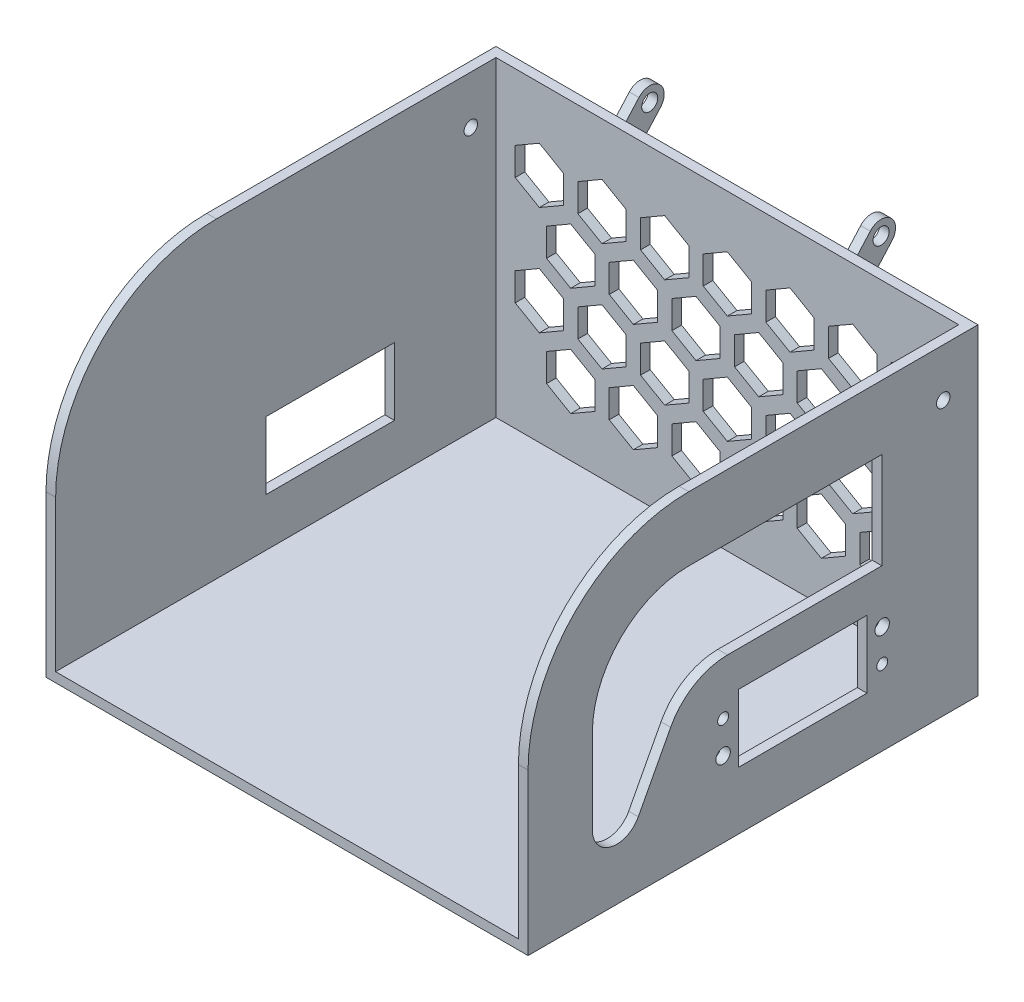
SolidWorks part; units mm, degrees
material "PLA"
ref_plane "Front Plane" through (0, 0, 0) normal (0, 0, 1) x (1, 0, 0)
ref_plane "Top Plane" through (0, 0, 0) normal (0, 1, 0) x (1, 0, 0)
ref_plane "Right Plane" through (0, 0, 0) normal (1, 0, 0) x (0, 0, -1)
sketch "Sketch1" plane through (0, 0, 0) normal (1, 0, 0) x (0, 0, -1)
  line L0 (0, 0) -> (-140, 0)
  line L1 (-140, 0) -> (-140, 50)
  line L2 (-90, 100) -> (0, 100)
  line L3 (0, 100) -> (0, 0)
  arc A0 (-140, 50) -> (-90, 100) centre (-90, 50) cw
  dimension "D1" = 140
  dimension "D2" = 100
  dimension "D3" = 50
extrude "Boss-Extrude1" add sketch "Sketch1" along normal blind 150 contours A0 L2 L3 L0 L1
sketch "Sketch2" plane through (0, 100, 0) normal (0, 1, 0) x (1, 0, 0)
  line L0 (150, 0) -> (0, 0) construction
  line L1 (3, -3) -> (147, -3)
  line L2 (3, -3) -> (3, -145)
  line L3 (3, -145) -> (147, -145)
  line L4 (147, -3) -> (147, -145)
  line L5 (150, -90) -> (150, 0) construction
  line L6 (0, -90) -> (0, 0) construction
  line L8 (150, -140) -> (0, -140) construction
  dimension "D1" = 3
  dimension "D2" = 3
  dimension "D3" = 3
  dimension "D4" = 5
extrude "Cut-Extrude1" cut sketch "Sketch2" against normal offset from surface (97 mm away) 3 up to face at (75, 0, 70)
ref_plane "Plane1" through (75, 0, 0) normal (1, 0, 0) x (0, 0, -1)
ref_plane "Plane2" through (111, 0, 0) normal (1, 0, 0) x (0, 0, -1)
ref_plane "Plane3" through (39, 0, 0) normal (1, 0, 0) x (0, 0, -1)
sketch "Sketch3" plane through (111, 0, 0) normal (1, 0, 0) x (0, 0, -1)
  line L0 (0, 100) -> (0, 86.4837)
  line L1 (0, 86.4837) -> (10.7098, 98.4837)
  line L2 (3.9952, 104.4764) -> (0, 100)
  arc A0 (10.7098, 98.4837) -> (3.9952, 104.4764) centre (7.3525, 101.4801) ccw
  circle A1 centre (7.3525, 101.4801) radius 2.5
  dimension "D1" = 2
  dimension "D2" = 5
  dimension "D3" = 6
  dimension "D4" = 12
extrude "Boss-Extrude2" add sketch "Sketch3" along normal mid plane 3
mirror "Mirror1" about plane through (75, 0, 0) normal (1, 0, 0) of "Boss-Extrude2"
sketch "Sketch4" plane through (150, 0, 0) normal (1, 0, 0) x (0, 0, -1)
  line L0 (-10.8107, 85.0634) -> (-67.3793, 28.4949) construction
  line L1 (-74.5612, 38.9949) -> (-74.5612, 17.9949)
  line L2 (-74.5612, 17.9949) -> (-34.5612, 17.9949)
  line L3 (0, 0) -> (-140, 0) construction
  line L4 (-34.5612, 17.9949) -> (-34.5612, 38.9949)
  line L5 (-34.5612, 38.9949) -> (-74.5612, 38.9949)
  circle A0 centre (-67.3793, 28.4949) radius 2.5
  circle A1 centre (-10.8107, 85.0634) radius 2.1
  point P8 (-74.5612, 28.4949)
  dimension "D4" = 4.2
  dimension "D5" = 5
  dimension "D1" = 80
  dimension "D2" = 45
  dimension "D3" = 40
  dimension "D6" = 21
extrude "Cut-Extrude2" cut sketch "Sketch4" against normal up to next contours A0 | A1 | L4 L5 A0 L1 L2 region at (150, 28.4949, 54.2544) region at (150, 28.4949, 67.3793) region at (150, 85.0634, 10.8107)
mirror "Mirror2" about plane through (75, 0, 0) normal (1, 0, 0) of "Cut-Extrude2"
sketch "Sketch5" plane through (0, 0, 0) normal (0, 0, -1) x (-1, 0, 0)
  line L0 (-150, 75) -> (0, 75) construction
  line L1 (-150, 100) -> (-150, 0) construction
  line L2 (0, 100) -> (0, 0) construction
  line L3 (-75, 100) -> (-75, 0) construction
  line L4 (-109.5, 100) -> (-40.5, 100) construction
  line L5 (-75, 91.3518) -> (-75, -91.3518) construction
  line L6 (-114, 83.6603) -> (-121.5, 79.3301)
  line L7 (-133.5, 83.6603) -> (-141, 79.3301)
  line L8 (-141, 79.3301) -> (-141, 70.6699)
  line L9 (-141, 70.6699) -> (-133.5, 66.3397)
  line L10 (-133.5, 66.3397) -> (-126, 70.6699)
  line L11 (-126, 70.6699) -> (-126, 79.3301)
  line L12 (-126, 79.3301) -> (-133.5, 83.6603)
  line L13 (-121.5, 79.3301) -> (-121.5, 70.6699)
  line L14 (-121.5, 70.6699) -> (-114, 66.3397)
  line L15 (-114, 66.3397) -> (-106.5, 70.6699)
  line L16 (-106.5, 70.6699) -> (-106.5, 79.3301)
  line L17 (-106.5, 79.3301) -> (-114, 83.6603)
  line L18 (-94.5, 83.6603) -> (-102, 79.3301)
  line L19 (-102, 79.3301) -> (-102, 70.6699)
  line L20 (-102, 70.6699) -> (-94.5, 66.3397)
  line L21 (-94.5, 66.3397) -> (-87, 70.6699)
  line L22 (-87, 70.6699) -> (-87, 79.3301)
  line L23 (-87, 79.3301) -> (-94.5, 83.6603)
  line L24 (-75, 83.6603) -> (-82.5, 79.3301)
  line L25 (-82.5, 79.3301) -> (-82.5, 70.6699)
  line L26 (-82.5, 70.6699) -> (-75, 66.3397)
  line L27 (-75, 66.3397) -> (-67.5, 70.6699)
  line L28 (-67.5, 70.6699) -> (-67.5, 79.3301)
  line L29 (-67.5, 79.3301) -> (-75, 83.6603)
  line L30 (-55.5, 83.6603) -> (-63, 79.3301)
  line L31 (-63, 79.3301) -> (-63, 70.6699)
  line L32 (-63, 70.6699) -> (-55.5, 66.3397)
  line L33 (-55.5, 66.3397) -> (-48, 70.6699)
  line L34 (-48, 70.6699) -> (-48, 79.3301)
  line L35 (-48, 79.3301) -> (-55.5, 83.6603)
  line L36 (-36, 83.6603) -> (-43.5, 79.3301)
  line L37 (-43.5, 79.3301) -> (-43.5, 70.6699)
  line L38 (-43.5, 70.6699) -> (-36, 66.3397)
  line L39 (-36, 66.3397) -> (-28.5, 70.6699)
  line L40 (-28.5, 70.6699) -> (-28.5, 79.3301)
  line L41 (-28.5, 79.3301) -> (-36, 83.6603)
  line L42 (-16.5, 83.6603) -> (-24, 79.3301)
  line L43 (-24, 79.3301) -> (-24, 70.6699)
  line L44 (-24, 70.6699) -> (-16.5, 66.3397)
  line L45 (-16.5, 66.3397) -> (-9, 70.6699)
  line L46 (-9, 70.6699) -> (-9, 79.3301)
  line L47 (-9, 79.3301) -> (-16.5, 83.6603)
  line L48 (-150, 58.1125) -> (0, 58.1125) construction
  line L49 (-123.75, 58.1125) -> (-123.75, 75) construction
  line L50 (-123.75, 66.7728) -> (-131.25, 62.4426)
  line L51 (-131.25, 62.4426) -> (-131.25, 53.7824)
  line L52 (-131.25, 53.7824) -> (-123.75, 49.4523)
  line L53 (-123.75, 49.4523) -> (-116.25, 53.7824)
  line L54 (-116.25, 53.7824) -> (-116.25, 62.4426)
  line L55 (-116.25, 62.4426) -> (-123.75, 66.7728)
  line L56 (-37.5, 100) -> (0, 100) construction
  line L57 (-104.25, 66.7728) -> (-111.75, 62.4426)
  line L58 (-111.75, 62.4426) -> (-111.75, 53.7824)
  line L59 (-111.75, 53.7824) -> (-104.25, 49.4523)
  line L60 (-104.25, 49.4523) -> (-96.75, 53.7824)
  line L61 (-96.75, 53.7824) -> (-96.75, 62.4426)
  line L62 (-96.75, 62.4426) -> (-104.25, 66.7728)
  line L63 (-84.75, 66.7728) -> (-92.25, 62.4426)
  line L64 (-92.25, 62.4426) -> (-92.25, 53.7824)
  line L65 (-92.25, 53.7824) -> (-84.75, 49.4523)
  line L66 (-84.75, 49.4523) -> (-77.25, 53.7824)
  line L67 (-77.25, 53.7824) -> (-77.25, 62.4426)
  line L68 (-77.25, 62.4426) -> (-84.75, 66.7728)
  line L69 (-65.25, 66.7728) -> (-72.75, 62.4426)
  line L70 (-72.75, 62.4426) -> (-72.75, 53.7824)
  line L71 (-72.75, 53.7824) -> (-65.25, 49.4523)
  line L72 (-65.25, 49.4523) -> (-57.75, 53.7824)
  line L73 (-57.75, 53.7824) -> (-57.75, 62.4426)
  line L74 (-57.75, 62.4426) -> (-65.25, 66.7728)
  line L75 (-45.75, 66.7728) -> (-53.25, 62.4426)
  line L76 (-53.25, 62.4426) -> (-53.25, 53.7824)
  line L77 (-53.25, 53.7824) -> (-45.75, 49.4523)
  line L78 (-45.75, 49.4523) -> (-38.25, 53.7824)
  line L79 (-38.25, 53.7824) -> (-38.25, 62.4426)
  line L80 (-38.25, 62.4426) -> (-45.75, 66.7728)
  line L81 (-26.25, 66.7728) -> (-33.75, 62.4426)
  line L82 (-33.75, 62.4426) -> (-33.75, 53.7824)
  line L83 (-33.75, 53.7824) -> (-26.25, 49.4523)
  line L84 (-26.25, 49.4523) -> (-18.75, 53.7824)
  line L85 (-18.75, 53.7824) -> (-18.75, 62.4426)
  line L86 (-18.75, 62.4426) -> (-26.25, 66.7728)
  line L87 (-9, 36.8949) -> (-16.5, 32.5648)
  line L88 (-9, 45.5551) -> (-9, 36.8949)
  line L89 (-16.5, 49.8853) -> (-9, 45.5551)
  line L90 (-24, 45.5551) -> (-16.5, 49.8853)
  line L91 (-24, 36.8949) -> (-24, 45.5551)
  line L92 (-16.5, 32.5648) -> (-24, 36.8949)
  line L93 (-28.5, 36.8949) -> (-36, 32.5648)
  line L94 (-28.5, 45.5551) -> (-28.5, 36.8949)
  line L95 (-36, 49.8853) -> (-28.5, 45.5551)
  line L96 (-43.5, 45.5551) -> (-36, 49.8853)
  line L97 (-43.5, 36.8949) -> (-43.5, 45.5551)
  line L98 (-36, 32.5648) -> (-43.5, 36.8949)
  line L99 (-48, 36.8949) -> (-55.5, 32.5648)
  line L100 (-48, 45.5551) -> (-48, 36.8949)
  line L101 (-55.5, 49.8853) -> (-48, 45.5551)
  line L102 (-63, 45.5551) -> (-55.5, 49.8853)
  line L103 (-63, 36.8949) -> (-63, 45.5551)
  line L104 (-55.5, 32.5648) -> (-63, 36.8949)
  line L105 (-67.5, 36.8949) -> (-75, 32.5648)
  line L106 (-67.5, 45.5551) -> (-67.5, 36.8949)
  line L107 (-75, 49.8853) -> (-67.5, 45.5551)
  line L108 (-82.5, 45.5551) -> (-75, 49.8853)
  line L109 (-82.5, 36.8949) -> (-82.5, 45.5551)
  line L110 (-75, 32.5648) -> (-82.5, 36.8949)
  line L111 (-87, 36.8949) -> (-94.5, 32.5648)
  line L112 (-87, 45.5551) -> (-87, 36.8949)
  line L113 (-94.5, 49.8853) -> (-87, 45.5551)
  line L114 (-102, 45.5551) -> (-94.5, 49.8853)
  line L115 (-102, 36.8949) -> (-102, 45.5551)
  line L116 (-94.5, 32.5648) -> (-102, 36.8949)
  line L117 (-106.5, 36.8949) -> (-114, 32.5648)
  line L118 (-106.5, 45.5551) -> (-106.5, 36.8949)
  line L119 (-114, 49.8853) -> (-106.5, 45.5551)
  line L120 (-121.5, 45.5551) -> (-114, 49.8853)
  line L121 (-121.5, 36.8949) -> (-121.5, 45.5551)
  line L122 (-114, 32.5648) -> (-121.5, 36.8949)
  line L123 (-126, 36.8949) -> (-133.5, 32.5648)
  line L124 (-126, 45.5551) -> (-126, 36.8949)
  line L125 (-133.5, 49.8853) -> (-126, 45.5551)
  line L126 (-141, 45.5551) -> (-133.5, 49.8853)
  line L127 (-141, 36.8949) -> (-141, 45.5551)
  line L128 (-133.5, 32.5648) -> (-141, 36.8949)
  line L129 (-141, 41.225) -> (-9, 41.225) construction
  line L130 (-18.75, 20.0074) -> (-26.25, 15.6773)
  line L131 (-18.75, 28.6676) -> (-18.75, 20.0074)
  line L132 (-26.25, 32.9978) -> (-18.75, 28.6676)
  line L133 (-33.75, 28.6676) -> (-26.25, 32.9978)
  line L134 (-33.75, 20.0074) -> (-33.75, 28.6676)
  line L135 (-26.25, 15.6773) -> (-33.75, 20.0074)
  line L136 (-38.25, 20.0074) -> (-45.75, 15.6773)
  line L137 (-38.25, 28.6676) -> (-38.25, 20.0074)
  line L138 (-45.75, 32.9978) -> (-38.25, 28.6676)
  line L139 (-53.25, 28.6676) -> (-45.75, 32.9978)
  line L140 (-53.25, 20.0074) -> (-53.25, 28.6676)
  line L141 (-45.75, 15.6773) -> (-53.25, 20.0074)
  line L142 (-57.75, 20.0074) -> (-65.25, 15.6773)
  line L143 (-57.75, 28.6676) -> (-57.75, 20.0074)
  line L144 (-65.25, 32.9978) -> (-57.75, 28.6676)
  line L145 (-72.75, 28.6676) -> (-65.25, 32.9978)
  line L146 (-72.75, 20.0074) -> (-72.75, 28.6676)
  line L147 (-65.25, 15.6773) -> (-72.75, 20.0074)
  line L148 (-77.25, 20.0074) -> (-84.75, 15.6773)
  line L149 (-77.25, 28.6676) -> (-77.25, 20.0074)
  line L150 (-84.75, 32.9978) -> (-77.25, 28.6676)
  line L151 (-92.25, 28.6676) -> (-84.75, 32.9978)
  line L152 (-92.25, 20.0074) -> (-92.25, 28.6676)
  line L153 (-84.75, 15.6773) -> (-92.25, 20.0074)
  line L154 (-96.75, 20.0074) -> (-104.25, 15.6773)
  line L155 (-96.75, 28.6676) -> (-96.75, 20.0074)
  line L156 (-104.25, 32.9978) -> (-96.75, 28.6676)
  line L157 (-111.75, 28.6676) -> (-104.25, 32.9978)
  line L158 (-111.75, 20.0074) -> (-111.75, 28.6676)
  line L159 (-104.25, 15.6773) -> (-111.75, 20.0074)
  line L160 (-116.25, 20.0074) -> (-123.75, 15.6773)
  line L161 (-116.25, 28.6676) -> (-116.25, 20.0074)
  line L162 (-123.75, 32.9978) -> (-116.25, 28.6676)
  line L163 (-131.25, 28.6676) -> (-123.75, 32.9978)
  line L164 (-131.25, 20.0074) -> (-131.25, 28.6676)
  line L165 (-123.75, 15.6773) -> (-131.25, 20.0074)
  circle A0 centre (-133.5, 75) radius 7.5 construction
  circle A1 centre (-123.75, 58.1125) radius 7.5 construction
  point P71 (-120, 64.6077)
  point P72 (-117.75, 68.5048)
  dimension "D2" = 15
  dimension "D3" = 9
  dimension "D4" = 9
  dimension "D5" = 25
  dimension "D6" = 4.5
  dimension "D8" = 18.75
  dimension "D1" = 7
  dimension "D7" = 6
extrude "Cut-Extrude3" cut sketch "Sketch5" against normal blind 10
hole_wizard "Taladro de margen para M31" positions "Croquis1" profile "Croquis2" hole size "M3" standard "Ansi Metric" end condition up to next
sketch "Croquis1" plane through (150, 0, 0) normal (1, 0, 0) x (0, 0, -1)
  point P0 (-79.3112, 33.4949)
  point P3 (-29.8112, 23.4949)
sketch "Croquis2" plane through (150, 33.4949, 79.3112) normal (0, 1, 0) x (0, 0, -1)
  line L0 (0, 0) -> (0, 3)
  line L1 (0, 3) -> (1.7, 3)
  line L2 (1.7, 3) -> (1.7, 0)
  line L5 (1.7, 0) -> (0, 0)
  line L11 (0, -6.35) -> (0, 107.95) construction
  dimension "Diámetro de taladro hasta el siguiente" = 3.4
  dimension "Profundidad de taladro hasta el siguiente" = 3
hole_wizard "Taladro de margen para M41" positions "Croquis3" profile "Croquis4" hole size "M4" standard "Ansi Metric" end condition up to next
sketch "Croquis3" plane through (150, 0, 0) normal (1, 0, 0) x (0, 0, -1)
  point P0 (-79.3112, 23.4949)
  point P3 (-29.8112, 33.4949)
sketch "Croquis4" plane through (150, 23.4949, 79.3112) normal (0, 1, 0) x (0, 0, -1)
  line L0 (0, 0) -> (0, 3)
  line L1 (0, 3) -> (2.25, 3)
  line L2 (2.25, 3) -> (2.25, 0)
  line L5 (2.25, 0) -> (0, 0)
  line L11 (0, -6.35) -> (0, 107.95) construction
  dimension "Diámetro de taladro hasta el siguiente" = 4.5
  dimension "Profundidad de taladro hasta el siguiente" = 3
sketch "Croquis5" plane through (147, 0, 0) normal (-1, 0, 0) x (0, 0, 1)
  line L4 (120, 50) -> (120, 23.7865)
  line L5 (105.6989, 20.2451) -> (90, 50)
  line L6 (90, 50) -> (29.9084, 50)
  line L7 (29.9084, 50) -> (29.9084, 80)
  line L8 (29.9084, 80) -> (90, 80)
  arc A5 (120, 23.7865) -> (105.6989, 20.2451) centre (112.411, 23.7865) cw
  arc A6 (120, 50) -> (90, 80) centre (90, 50) ccw
  arc A7 (120, 50) -> (90, 80) centre (90, 50) ccw
  dimension "D1" = 20
extrude "Cortar-Extruir1" cut sketch "Croquis5" against normal up to next
fillet "Redondeo1" radius 20 1 edges at (148.5, 50, 90)
equation "\"forward_length\"= 130"
equation "\"height\"= 100"
equation "\"eslabon_AB\"=80"
